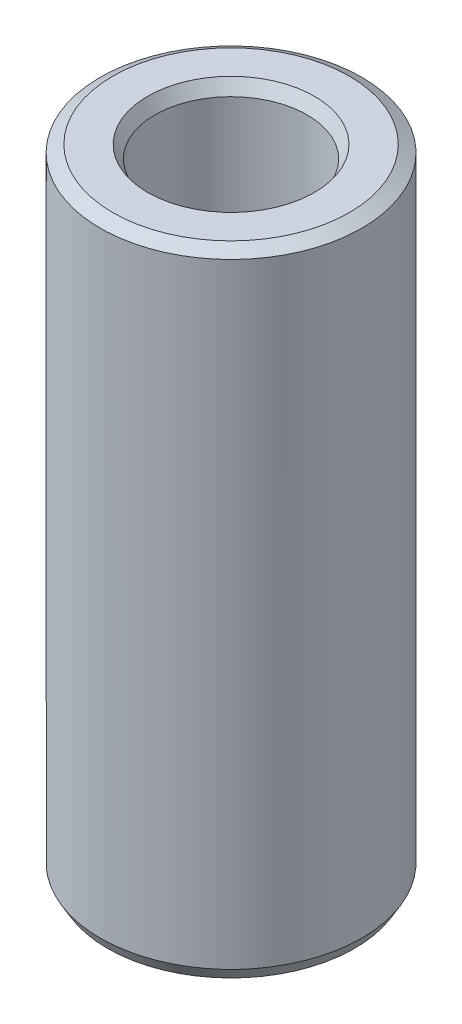
SolidWorks part; units mm, degrees
ref_plane "Front Plane" through (0, 0, 0) normal (0, 0, 1) x (1, 0, 0)
ref_plane "Top Plane" through (0, 0, 0) normal (0, 1, 0) x (1, 0, 0)
ref_plane "Right Plane" through (0, 0, 0) normal (1, 0, 0) x (0, 0, -1)
sketch "Sketch1" plane through (0, 0, 0) normal (0, 1, 0) x (1, 0, 0)
  circle A0 centre (0, 0) radius 55
  dimension "SLEEVE_OD" = 110
extrude "Boss-Extrude1" add sketch "Sketch1" along normal blind 266.8773
sketch "Sketch2" plane through (0, 0, 0) normal (0, 1, 0) x (1, 0, 0)
  circle A0 centre (0, 0) radius 32.0304
  dimension "BORE_D" = 64.0608
extrude "Cut-Extrude1" cut sketch "Sketch2" along normal through all
chamfer "Chamfer1" distance 3.0442 angle 60 4 edges at (0, 266.8773, 32.0304) (0, 0, 32.0304) (0, 0, 55) (0, 266.8773, 55) first distance on face at (0, 266.8773, 32.0304) first distance on face at (0, 0, 32.0304) first distance on face at (0, 266.8773, 55)
